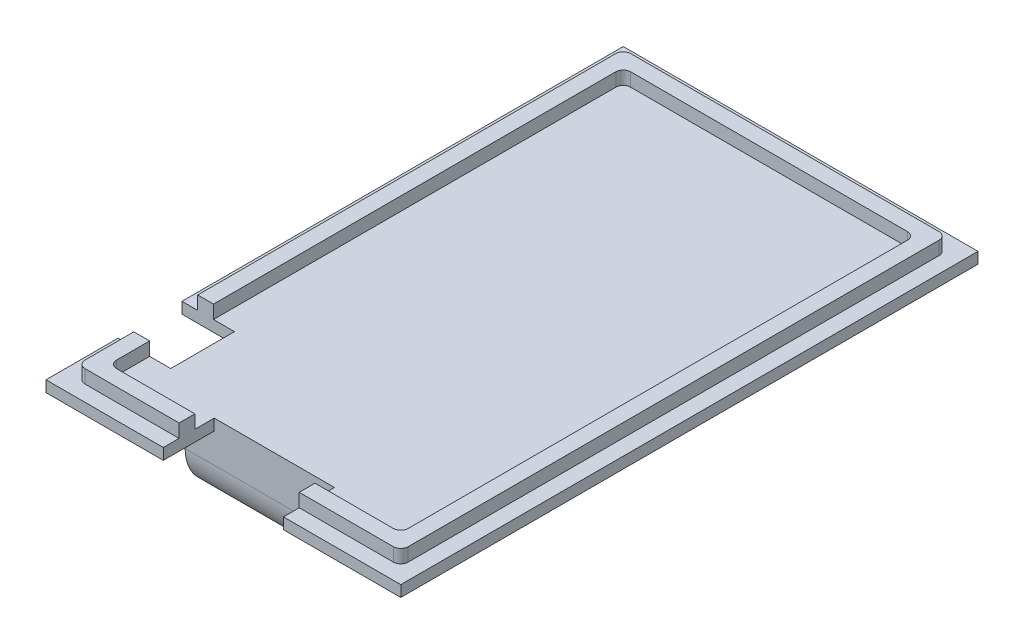
SolidWorks part; units mm, degrees
ref_plane "Front Plane" through (0, 0, 0) normal (0, 0, 1) x (1, 0, 0)
ref_plane "Top Plane" through (0, 0, 0) normal (0, 1, 0) x (1, 0, 0)
ref_plane "Right Plane" through (0, 0, 0) normal (1, 0, 0) x (0, 0, -1)
sketch "PCB Dimensions" plane through (0, 0, 0) normal (0, 1, 0) x (1, 0, 0)
  line L0 (0, 0) -> (-3.5355, 3.5355)
  line L1 (0, 0) -> (40.6457, 0)
  line L2 (0, 0) -> (0, -70.5657)
  line L3 (0, -70.5657) -> (40.6457, -70.5657)
  line L4 (40.6457, 0) -> (40.6457, -70.5657)
  line L5 (40.6457, -70.5657) -> (44.1812, -74.1012)
  line L6 (40.6457, 0) -> (44.1812, 3.5355)
  line L11 (0, -70.5657) -> (-3.5355, -74.1012)
  line L12 (44.1812, -74.1012) -> (-3.5355, -74.1012)
  line L13 (44.1812, -74.1012) -> (44.1812, 3.5355)
  line L14 (44.1812, 3.5355) -> (-3.5355, 3.5355)
  line L15 (-3.5355, -74.1012) -> (-3.5355, 3.5355)
extrude "Boss-Extrude3" add sketch "PCB Dimensions" along normal blind 1.5 contours L14 L15 L12 L13
sketch "Sketch5" plane through (0, 1.5, 0) normal (0, 1, 0) x (1, 0, 0)
  line L11 (-1.4142, 1.4142) -> (42.0599, 1.4142)
  line L12 (-1.4142, 1.4142) -> (-1.4142, -71.9799)
  line L13 (-1.4142, -71.9799) -> (42.0599, -71.9799)
  line L14 (42.0599, 1.4142) -> (42.0599, -71.9799)
  line L17 (0.7071, -0.7071) -> (39.9386, -0.7071)
  line L18 (0.7071, -0.7071) -> (0.7071, -69.8586)
  line L19 (0.7071, -69.8586) -> (39.9386, -69.8586)
  line L20 (39.9386, -0.7071) -> (39.9386, -69.8586)
extrude "Boss-Extrude4" add sketch "Sketch5" along normal blind 1.8 contours L13 L14 L11 L12 | L18 L19 L20 L17
fillet "Fillet1" radius 1 8 edges at (0.7071, 2.4, 69.8586) (-1.4142, 2.4, 71.9799) (39.9386, 2.4, 69.8586) (42.0599, 2.4, 71.9799) (0.7071, 2.4, 0.7071) (39.9386, 2.4, 0.7071) (42.0599, 2.4, -1.4142) (-1.4142, 2.4, -1.4142)
sketch "Sketch6" plane through (0, 0, 0) normal (0, -1, 0) x (1, 0, 0)
  line L0 (8.3228, 67.2497) -> (32.3228, 67.2497)
  line L1 (8.3228, 67.2497) -> (8.3228, 3.2497)
  line L2 (8.3228, 3.2497) -> (32.3228, 3.2497)
  line L3 (32.3228, 67.2497) -> (32.3228, 3.2497)
  line L4 (20.3228, 74.1012) -> (20.3228, -3.5355)
  line L5 (44.1812, 74.1012) -> (-3.5355, 74.1012) construction
  line L6 (44.1812, -3.5355) -> (-3.5355, -3.5355) construction
  line L7 (-3.5355, 35.2828) -> (44.1812, 35.2828)
  line L8 (-3.5355, 74.1012) -> (-3.5355, -3.5355) construction
  line L9 (44.1812, 74.1012) -> (44.1812, -3.5355) construction
extrude "Boss-Extrude5" add sketch "Sketch6" along normal blind 10 contours L1 L7 L4 L0 | L4 L7 L3 L0 | L7 L1 L2 L4 | L7 L4 L2 L3 region at (14.3228, 0, 51.2663) region at (26.3228, 0, 51.2663) region at (14.3228, 0, 19.2663) region at (26.3228, 0, 19.2663)
sketch "Sketch7" plane through (32.3228, 0, 0) normal (1, 0, 0) x (0, 0, -1)
  line L0 (-59.2497, 0) -> (-11.2497, 0)
  line L1 (-59.2497, 0) -> (-59.2497, -6)
  line L2 (-59.2497, -6) -> (-11.2497, -6)
  line L3 (-11.2497, 0) -> (-11.2497, -6)
extrude "Cut-Extrude1" cut sketch "Sketch7" against normal blind 24
fillet "Fillet2" radius 6 2 edges at (20.3228, -10, 3.2497) (20.3228, -10, 67.2497)
fillet "Fillet3" radius 1 2 edges at (20.3228, -6, 11.2497) (20.3228, -6, 59.2497)
scale "Scale1" bodies to scale 112 scale about centroid uniform scaling yes scale factor 0.99
sketch "Sketch8" plane through (0, -0.0322, 0) normal (0, -1, 0) x (1, 0, 0)
  line L1 (43.9426, 73.7128) -> (-3.297, 73.7128) construction
  line L2 (20.3228, 73.7128) -> (12.3228, 73.7128)
  line L3 (20.3228, 73.7128) -> (28.3228, 73.7128)
  line L4 (28.3228, 73.7128) -> (28.3228, 66.9299)
  line L5 (8.4428, 66.9299) -> (32.2028, 66.9299) construction
  line L6 (12.3228, 73.7128) -> (12.3228, 66.9299)
  line L7 (12.3228, 66.9299) -> (28.3228, 66.9299)
extrude "Cut-Extrude2" cut sketch "Sketch8" against normal blind 10
sketch "Sketch9" plane through (0, -0.0322, 0) normal (0, -1, 0) x (1, 0, 0)
  line L1 (-3.297, 55.6128) -> (3.703, 55.6128)
  line L2 (-3.297, 64.1128) -> (-3.297, 55.6128)
  line L3 (-3.297, 64.1128) -> (3.703, 64.1128)
  line L4 (3.703, 64.1128) -> (3.703, 55.6128)
extrude "Cut-Extrude3" cut sketch "Sketch9" against normal blind 10
